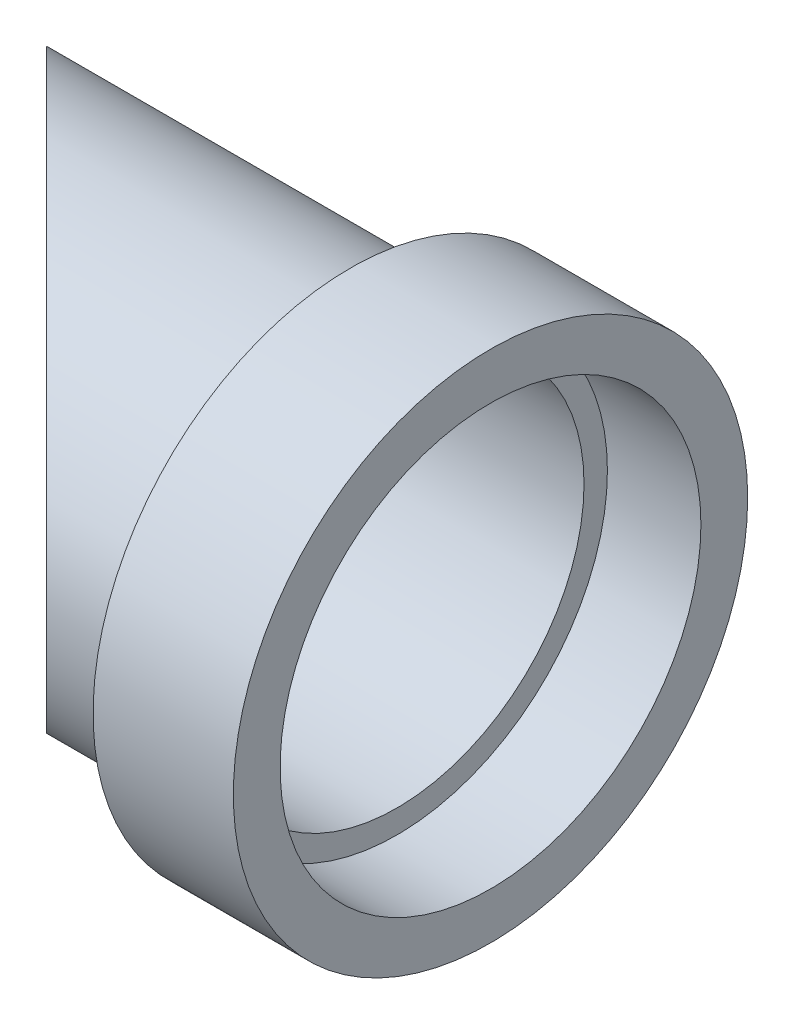
SolidWorks part; units mm, degrees
ref_plane "Front Plane" through (0, 0, 0) normal (0, 0, 1) x (1, 0, 0)
ref_plane "Top Plane" through (0, 0, 0) normal (0, 1, 0) x (1, 0, 0)
ref_plane "Right Plane" through (0, 0, 0) normal (1, 0, 0) x (0, 0, -1)
sketch "Sketch3" plane through (0, 0, 0) normal (1, 0, 0) x (0, 0, -1)
  circle A0 centre (0, 0) radius 57.15
  circle A1 centre (0, 0) radius 50.8
  dimension "D1" = 114.3
  dimension "D2" = 101.6
extrude "Boss-Extrude2" add sketch "Sketch3" along normal blind 152.4
sketch "Sketch4" plane through (152.4, 0, 0) normal (1, 0, 0) x (0, 0, -1)
  circle A0 centre (0, 0) radius 69.85
  circle A1 centre (0, 0) radius 57.15 construction
  circle A2 centre (0, 0) radius 57.15
  dimension "D1" = 12.7
extrude "Boss-Extrude3" add sketch "Sketch4" along normal blind 25.4 and the other way blind 12.7
sketch "Sketch5" plane through (0, 0, 0) normal (0, 1, 0) x (1, 0, 0)
  line L0 (0, -57.15) -> (114.3, -57.15)
  line L1 (0, -57.15) -> (139.7, -57.15) construction
  line L2 (114.3, -57.15) -> (0, 57.15)
  line L3 (0, 57.15) -> (0, -57.15)
  dimension "D1" = 114.3
extrude "Cut-Extrude1" cut sketch "Sketch5" against normal blind 127 and the other way blind 127
